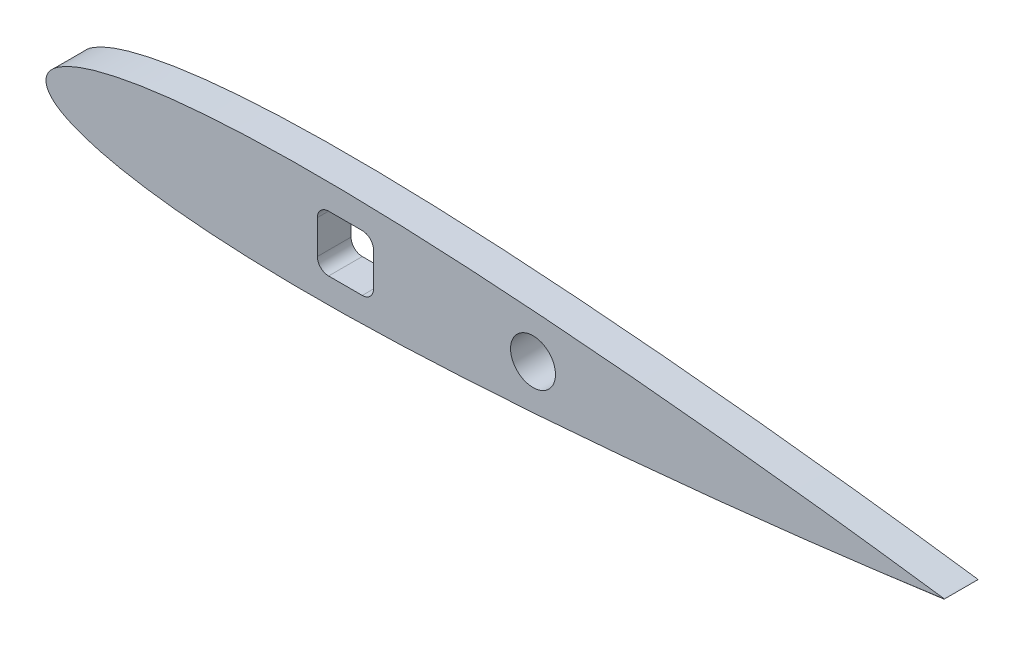
SolidWorks part; units mm, degrees
ref_plane "Plano frontal" through (0, 0, 0) normal (0, 0, 1) x (1, 0, 0)
ref_plane "Plano superior" through (0, 0, 0) normal (0, 1, 0) x (1, 0, 0)
ref_plane "Plano direito" through (0, 0, 0) normal (1, 0, 0) x (0, 0, -1)
curve "Curva1"
  spline degree 3 poles (159.0085, -0.1375, 0) (160.9309, 0, 0) (159.0085, 0.1375, 0) (158.4244, 0.2215, 0) (158.1443, 0.2603, 0) (157.6844, 0.3248, 0) (157.0391, 0.4145, 0) (156.2132, 0.5284, 0) (155.2073, 0.6667, 0) (154.0242, 0.8279, 0) (152.6664, 1.0108, 0) (151.1374, 1.2148, 0) (149.4405, 1.4383, 0) (147.5798, 1.6803, 0) (145.5596, 1.9389, 0) (143.3846, 2.2135, 0) (141.0599, 2.502, 0) (138.5909, 2.803, 0) (135.9835, 3.1151, 0) (133.2436, 3.4368, 0) (130.3776, 3.7661, 0) (127.3924, 4.1022, 0) (124.2948, 4.4425, 0) (121.0922, 4.7864, 0) (117.7919, 5.1312, 0) (114.4017, 5.4763, 0) (110.9294, 5.8191, 0) (107.3833, 6.1585, 0) (103.7715, 6.4922, 0) (100.1026, 6.819, 0) (96.385, 7.1362, 0) (92.6275, 7.4425, 0) (88.8388, 7.7359, 0) (85.0279, 8.0139, 0) (81.2035, 8.275, 0) (77.3747, 8.5169, 0) (73.5504, 8.7374, 0) (69.7394, 8.9347, 0) (65.9507, 9.1067, 0) (62.1931, 9.2514, 0) (58.4755, 9.3672, 0) (54.8064, 9.4521, 0) (51.1945, 9.5046, 0) (47.6482, 9.5231, 0) (44.1757, 9.5067, 0) (40.7852, 9.4546, 0) (37.4846, 9.3651, 0) (34.2816, 9.2387, 0) (31.1837, 9.0744, 0) (28.198, 8.8728, 0) (25.3316, 8.6339, 0) (22.5912, 8.3581, 0) (19.9831, 8.0464, 0) (17.5133, 7.7002, 0) (15.1877, 7.32, 0) (13.0116, 6.9078, 0) (10.9899, 6.4651, 0) (9.1275, 5.9934, 0) (7.4284, 5.4948, 0) (5.8964, 4.971, 0) (4.5348, 4.4239, 0) (3.3462, 3.8549, 0) (2.3329, 3.2652, 0) (1.496, 2.6559, 0) (0.8373, 2.026, 0) (0.3583, 1.3736, 0) (0.0654, 0.6956, 0) (-0.0319, 0, 0) (0.0654, -0.6956, 0) (0.3583, -1.3736, 0) (0.8373, -2.026, 0) (1.496, -2.6559, 0) (2.3329, -3.2652, 0) (3.3462, -3.8549, 0) (4.5348, -4.4239, 0) (5.8964, -4.971, 0) (7.4284, -5.4948, 0) (9.1275, -5.9934, 0) (10.9899, -6.4651, 0) (13.0116, -6.9078, 0) (15.1877, -7.32, 0) (17.5133, -7.7002, 0) (19.9831, -8.0464, 0) (22.5912, -8.3581, 0) (25.3316, -8.6339, 0) (28.198, -8.8728, 0) (31.1837, -9.0744, 0) (34.2816, -9.2387, 0) (37.4846, -9.3651, 0) (40.7852, -9.4546, 0) (44.1757, -9.5067, 0) (47.6482, -9.5231, 0) (51.1945, -9.5046, 0) (54.8064, -9.4521, 0) (58.4755, -9.3672, 0) (62.1931, -9.2514, 0) (65.9507, -9.1067, 0) (69.7394, -8.9347, 0) (73.5504, -8.7374, 0) (77.3747, -8.5169, 0) (81.2035, -8.275, 0) (85.0279, -8.0139, 0) (88.8388, -7.7359, 0) (92.6275, -7.4425, 0) (96.385, -7.1362, 0) (100.1026, -6.819, 0) (103.7715, -6.4922, 0) (107.3833, -6.1585, 0) (110.9294, -5.8191, 0) (114.4017, -5.4763, 0) (117.7919, -5.1312, 0) (121.0922, -4.7864, 0) (124.2948, -4.4425, 0) (127.3924, -4.1022, 0) (130.3776, -3.7661, 0) (133.2436, -3.4368, 0) (135.9835, -3.1151, 0) (138.5909, -2.803, 0) (141.0599, -2.502, 0) (143.3846, -2.2135, 0) (145.5596, -1.9389, 0) (147.5798, -1.6803, 0) (149.4405, -1.4383, 0) (151.1374, -1.2148, 0) (152.6664, -1.0108, 0) (154.0242, -0.8279, 0) (155.2073, -0.6667, 0) (156.2132, -0.5284, 0) (157.0391, -0.4145, 0) (157.6844, -0.3248, 0) (158.1443, -0.2603, 0) (158.4244, -0.2215, 0) (159.0085, -0.1375, 0) (160.9309, 0, 0) (159.0085, 0.1375, 0) knots -0.00555 -0.004691 -0.004405 0 0.004405 0.004691 0.00555 0.00698 0.008976 0.011535 0.014649 0.018312 0.022515 0.027248 0.032498 0.038254 0.044502 0.051227 0.058413 0.066043 0.074099 0.082562 0.091412 0.100627 0.110187 0.120068 0.130247 0.140701 0.151404 0.162332 0.173459 0.184758 0.196204 0.207769 0.219426 0.231148 0.242906 0.254675 0.266426 0.278132 0.289766 0.301302 0.312712 0.323969 0.33505 0.345929 0.356581 0.366982 0.37711 0.386942 0.396458 0.405637 0.414459 0.422907 0.430963 0.438612 0.445838 0.45263 0.458976 0.464866 0.470294 0.475255 0.479749 0.483781 0.487363 0.490516 0.493279 0.495712 0.49791 0.5 0.50209 0.504288 0.506721 0.509484 0.512637 0.516219 0.520251 0.524745 0.529706 0.535134 0.541024 0.54737 0.554162 0.561388 0.569037 0.577093 0.585541 0.594363 0.603542 0.613058 0.62289 0.633018 0.643419 0.654071 0.66495 0.676031 0.687288 0.698698 0.710234 0.721868 0.733574 0.745325 0.757094 0.768852 0.780574 0.792231 0.803796 0.815242 0.826541 0.837668 0.848596 0.859299 0.869753 0.879932 0.889813 0.899373 0.908588 0.917438 0.925901 0.933957 0.941587 0.948773 0.955498 0.961746 0.967502 0.972752 0.977485 0.981688 0.985351 0.988465 0.991024 0.99302 0.99445 0.995309 0.995595 1 1.004405 1.004691 1.00555 periodic
sketch "Esboço1" plane through (0, 0, 0) normal (0, 0, 1) x (1, 0, 0)
  line L0 (160, 0) -> (82, 0) construction
  line L1 (160, 0) -> (53.3333, 0) construction
  line L2 (0, 0) -> (15, 0) construction
  line L4 (56.3333, -5) -> (50.3333, -5)
  line L5 (58.3333, -3) -> (58.3333, 3)
  line L6 (56.3333, 5) -> (50.3333, 5)
  line L7 (48.3333, -3) -> (48.3333, 3)
  line L8 (58.3333, -5) -> (48.3333, 5) construction
  line L9 (58.3333, 5) -> (48.3333, -5) construction
  line L10 (13, -4) -> (17, -4)
  line L11 (11, -2) -> (11, 2)
  line L12 (13, 4) -> (17, 4)
  line L13 (19, -2) -> (19, 2)
  line L14 (11, -4) -> (19, 4) construction
  line L15 (11, 4) -> (19, -4) construction
  arc A0 (82, 8.219) -> (82, -8.219) centre (86.7452, 0) ccw construction
  arc A1 (78.9243, 8.418) -> (78.9243, -8.418) centre (86.7452, 0) ccw construction
  arc A2 (81, 9.951) -> (81, -9.951) centre (86.7452, 0) ccw construction
  circle A3 centre (86.7452, 0) radius 4
  arc A4 (50.3333, -5) -> (48.3333, -3) centre (50.3333, -3) cw
  arc A5 (56.3333, -5) -> (58.3333, -3) centre (56.3333, -3) ccw
  arc A6 (58.3333, 3) -> (56.3333, 5) centre (56.3333, 3) ccw
  arc A7 (50.3333, 5) -> (48.3333, 3) centre (50.3333, 3) ccw
  arc A8 (13, -4) -> (11, -2) centre (13, -2) cw
  arc A9 (17, -4) -> (19, -2) centre (17, -2) ccw
  arc A10 (17, 4) -> (19, 2) centre (17, 2) cw
  arc A11 (11, 2) -> (13, 4) centre (13, 2) cw
  spline S0 degree 3 poles (159.0085, -0.1375) (160.9309, 0) (159.0085, 0.1375) (158.4244, 0.2215) (158.1443, 0.2603) (157.6844, 0.3248) (157.0391, 0.4145) (156.2132, 0.5284) (155.2073, 0.6667) (154.0242, 0.8279) (152.6664, 1.0108) (151.1374, 1.2148) (149.4405, 1.4383) (147.5798, 1.6803) (145.5596, 1.9389) (143.3846, 2.2135) (141.0599, 2.502) (138.5909, 2.803) (135.9835, 3.1151) (133.2436, 3.4368) (130.3776, 3.7661) (127.3924, 4.1022) (124.2948, 4.4425) (121.0922, 4.7864) (117.7919, 5.1312) (114.4017, 5.4763) (110.9294, 5.8191) (107.3833, 6.1585) (103.7715, 6.4922) (100.1026, 6.819) (96.385, 7.1362) (92.6275, 7.4425) (88.8388, 7.7359) (85.0279, 8.0139) (81.2035, 8.275) (77.3747, 8.5169) (73.5504, 8.7374) (69.7394, 8.9347) (65.9507, 9.1067) (62.1931, 9.2514) (58.4755, 9.3672) (54.8064, 9.4521) (51.1945, 9.5046) (47.6482, 9.5231) (44.1757, 9.5067) (40.7852, 9.4546) (37.4846, 9.3651) (34.2816, 9.2387) (31.1837, 9.0744) (28.198, 8.8728) (25.3316, 8.6339) (22.5912, 8.3581) (19.9831, 8.0464) (17.5133, 7.7002) (15.1877, 7.32) (13.0116, 6.9078) (10.9899, 6.4651) (9.1275, 5.9934) (7.4284, 5.4948) (5.8964, 4.971) (4.5348, 4.4239) (3.3462, 3.8549) (2.3329, 3.2652) (1.496, 2.6559) (0.8373, 2.026) (0.3583, 1.3736) (0.0654, 0.6956) (-0.0319, 0) (0.0654, -0.6956) (0.3583, -1.3736) (0.8373, -2.026) (1.496, -2.6559) (2.3329, -3.2652) (3.3462, -3.8549) (4.5348, -4.4239) (5.8964, -4.971) (7.4284, -5.4948) (9.1275, -5.9934) (10.9899, -6.4651) (13.0116, -6.9078) (15.1877, -7.32) (17.5133, -7.7002) (19.9831, -8.0464) (22.5912, -8.3581) (25.3316, -8.6339) (28.198, -8.8728) (31.1837, -9.0744) (34.2816, -9.2387) (37.4846, -9.3651) (40.7852, -9.4546) (44.1757, -9.5067) (47.6482, -9.5231) (51.1945, -9.5046) (54.8064, -9.4521) (58.4755, -9.3672) (62.1931, -9.2514) (65.9507, -9.1067) (69.7394, -8.9347) (73.5504, -8.7374) (77.3747, -8.5169) (81.2035, -8.275) (85.0279, -8.0139) (88.8388, -7.7359) (92.6275, -7.4425) (96.385, -7.1362) (100.1026, -6.819) (103.7715, -6.4922) (107.3833, -6.1585) (110.9294, -5.8191) (114.4017, -5.4763) (117.7919, -5.1312) (121.0922, -4.7864) (124.2948, -4.4425) (127.3924, -4.1022) (130.3776, -3.7661) (133.2436, -3.4368) (135.9835, -3.1151) (138.5909, -2.803) (141.0599, -2.502) (143.3846, -2.2135) (145.5596, -1.9389) (147.5798, -1.6803) (149.4405, -1.4383) (151.1374, -1.2148) (152.6664, -1.0108) (154.0242, -0.8279) (155.2073, -0.6667) (156.2132, -0.5284) (157.0391, -0.4145) (157.6844, -0.3248) (158.1443, -0.2603) (158.4244, -0.2215) (159.0085, -0.1375) (160.9309, 0) (159.0085, 0.1375) knots -0.00555 -0.004691 -0.004405 0 0.004405 0.004691 0.00555 0.00698 0.008976 0.011535 0.014649 0.018312 0.022515 0.027248 0.032498 0.038254 0.044502 0.051227 0.058413 0.066043 0.074099 0.082562 0.091412 0.100627 0.110187 0.120068 0.130247 0.140701 0.151404 0.162332 0.173459 0.184758 0.196204 0.207769 0.219426 0.231148 0.242906 0.254675 0.266426 0.278132 0.289766 0.301302 0.312712 0.323969 0.33505 0.345929 0.356581 0.366982 0.37711 0.386942 0.396458 0.405637 0.414459 0.422907 0.430963 0.438612 0.445838 0.45263 0.458976 0.464866 0.470294 0.475255 0.479749 0.483781 0.487363 0.490516 0.493279 0.495712 0.49791 0.5 0.50209 0.504288 0.506721 0.509484 0.512637 0.516219 0.520251 0.524745 0.529706 0.535134 0.541024 0.54737 0.554162 0.561388 0.569037 0.577093 0.585541 0.594363 0.603542 0.613058 0.62289 0.633018 0.643419 0.654071 0.66495 0.676031 0.687288 0.698698 0.710234 0.721868 0.733574 0.745325 0.757094 0.768852 0.780574 0.792231 0.803796 0.815242 0.826541 0.837668 0.848596 0.859299 0.869753 0.879932 0.889813 0.899373 0.908588 0.917438 0.925901 0.933957 0.941587 0.948773 0.955498 0.961746 0.967502 0.972752 0.977485 0.981688 0.985351 0.988465 0.991024 0.99302 0.99445 0.995309 0.995595 1 1.004405 1.004691 1.00555 only from (160, 0) to (160, 0) construction
  spline S1 degree 3 poles (159.0085, -0.1375) (160.9309, 0) (159.0085, 0.1375) (158.4244, 0.2215) (158.1443, 0.2603) (157.6844, 0.3248) (157.0391, 0.4145) (156.2132, 0.5284) (155.2073, 0.6667) (154.0242, 0.8279) (152.6664, 1.0108) (151.1374, 1.2148) (149.4405, 1.4383) (147.5798, 1.6803) (145.5596, 1.9389) (143.3846, 2.2135) (141.0599, 2.502) (138.5909, 2.803) (135.9835, 3.1151) (133.2436, 3.4368) (130.3776, 3.7661) (127.3924, 4.1022) (124.2948, 4.4425) (121.0922, 4.7864) (117.7919, 5.1312) (114.4017, 5.4763) (110.9294, 5.8191) (107.3833, 6.1585) (103.7715, 6.4922) (100.1026, 6.819) (96.385, 7.1362) (92.6275, 7.4425) (88.8388, 7.7359) (85.0279, 8.0139) (81.2035, 8.275) (77.3747, 8.5169) (73.5504, 8.7374) (69.7394, 8.9347) (65.9507, 9.1067) (62.1931, 9.2514) (58.4755, 9.3672) (54.8064, 9.4521) (51.1945, 9.5046) (47.6482, 9.5231) (44.1757, 9.5067) (40.7852, 9.4546) (37.4846, 9.3651) (34.2816, 9.2387) (31.1837, 9.0744) (28.198, 8.8728) (25.3316, 8.6339) (22.5912, 8.3581) (19.9831, 8.0464) (17.5133, 7.7002) (15.1877, 7.32) (13.0116, 6.9078) (10.9899, 6.4651) (9.1275, 5.9934) (7.4284, 5.4948) (5.8964, 4.971) (4.5348, 4.4239) (3.3462, 3.8549) (2.3329, 3.2652) (1.496, 2.6559) (0.8373, 2.026) (0.3583, 1.3736) (0.0654, 0.6956) (-0.0319, 0) (0.0654, -0.6956) (0.3583, -1.3736) (0.8373, -2.026) (1.496, -2.6559) (2.3329, -3.2652) (3.3462, -3.8549) (4.5348, -4.4239) (5.8964, -4.971) (7.4284, -5.4948) (9.1275, -5.9934) (10.9899, -6.4651) (13.0116, -6.9078) (15.1877, -7.32) (17.5133, -7.7002) (19.9831, -8.0464) (22.5912, -8.3581) (25.3316, -8.6339) (28.198, -8.8728) (31.1837, -9.0744) (34.2816, -9.2387) (37.4846, -9.3651) (40.7852, -9.4546) (44.1757, -9.5067) (47.6482, -9.5231) (51.1945, -9.5046) (54.8064, -9.4521) (58.4755, -9.3672) (62.1931, -9.2514) (65.9507, -9.1067) (69.7394, -8.9347) (73.5504, -8.7374) (77.3747, -8.5169) (81.2035, -8.275) (85.0279, -8.0139) (88.8388, -7.7359) (92.6275, -7.4425) (96.385, -7.1362) (100.1026, -6.819) (103.7715, -6.4922) (107.3833, -6.1585) (110.9294, -5.8191) (114.4017, -5.4763) (117.7919, -5.1312) (121.0922, -4.7864) (124.2948, -4.4425) (127.3924, -4.1022) (130.3776, -3.7661) (133.2436, -3.4368) (135.9835, -3.1151) (138.5909, -2.803) (141.0599, -2.502) (143.3846, -2.2135) (145.5596, -1.9389) (147.5798, -1.6803) (149.4405, -1.4383) (151.1374, -1.2148) (152.6664, -1.0108) (154.0242, -0.8279) (155.2073, -0.6667) (156.2132, -0.5284) (157.0391, -0.4145) (157.6844, -0.3248) (158.1443, -0.2603) (158.4244, -0.2215) (159.0085, -0.1375) (160.9309, 0) (159.0085, 0.1375) knots -0.00555 -0.004691 -0.004405 0 0.004405 0.004691 0.00555 0.00698 0.008976 0.011535 0.014649 0.018312 0.022515 0.027248 0.032498 0.038254 0.044502 0.051227 0.058413 0.066043 0.074099 0.082562 0.091412 0.100627 0.110187 0.120068 0.130247 0.140701 0.151404 0.162332 0.173459 0.184758 0.196204 0.207769 0.219426 0.231148 0.242906 0.254675 0.266426 0.278132 0.289766 0.301302 0.312712 0.323969 0.33505 0.345929 0.356581 0.366982 0.37711 0.386942 0.396458 0.405637 0.414459 0.422907 0.430963 0.438612 0.445838 0.45263 0.458976 0.464866 0.470294 0.475255 0.479749 0.483781 0.487363 0.490516 0.493279 0.495712 0.49791 0.5 0.50209 0.504288 0.506721 0.509484 0.512637 0.516219 0.520251 0.524745 0.529706 0.535134 0.541024 0.54737 0.554162 0.561388 0.569037 0.577093 0.585541 0.594363 0.603542 0.613058 0.62289 0.633018 0.643419 0.654071 0.66495 0.676031 0.687288 0.698698 0.710234 0.721868 0.733574 0.745325 0.757094 0.768852 0.780574 0.792231 0.803796 0.815242 0.826541 0.837668 0.848596 0.859299 0.869753 0.879932 0.889813 0.899373 0.908588 0.917438 0.925901 0.933957 0.941587 0.948773 0.955498 0.961746 0.967502 0.972752 0.977485 0.981688 0.985351 0.988465 0.991024 0.99302 0.99445 0.995309 0.995595 1 1.004405 1.004691 1.00555 only from (160, 0) to (160, 0)
  point P47 (0, 0)
  dimension "D5" = 8
  dimension "D8" = 2
  dimension "D11" = 2
  dimension "D1" = 78
  dimension "D2" = 106.6667
  dimension "D3" = 15
  dimension "D6" = 10
  dimension "D7" = 10
  dimension "D9" = 8
  dimension "D10" = 8
  dimension "D4" = 2
extrude "Ressalto-extrusão1" add sketch "Esboço1" along normal blind 6 contours S1
extrude "Corte-extrusão1" cut sketch "Esboço1<5>" along normal through all contours L4 A4 L7 A7 L6 A6 L5 A5
sketch "Esboço1<5>" plane through (0, 0, 0) normal (0, 0, 1) x (1, 0, 0) same geometry as "Esboço1"
extrude "Corte-extrusão2" cut sketch "Esboço1<6>" along normal blind 2 contours L11 A11 L12 A10 L13 A9 L10 A8
sketch "Esboço1<6>" plane through (0, 0, 0) normal (0, 0, 1) x (1, 0, 0) same geometry as "Esboço1"
extrude "Corte-extrusão4" cut sketch "Esboço1<10>" along normal blind 10 contours A3
sketch "Esboço1<10>" plane through (0, 0, 0) normal (0, 0, 1) x (1, 0, 0) same geometry as "Esboço1"
